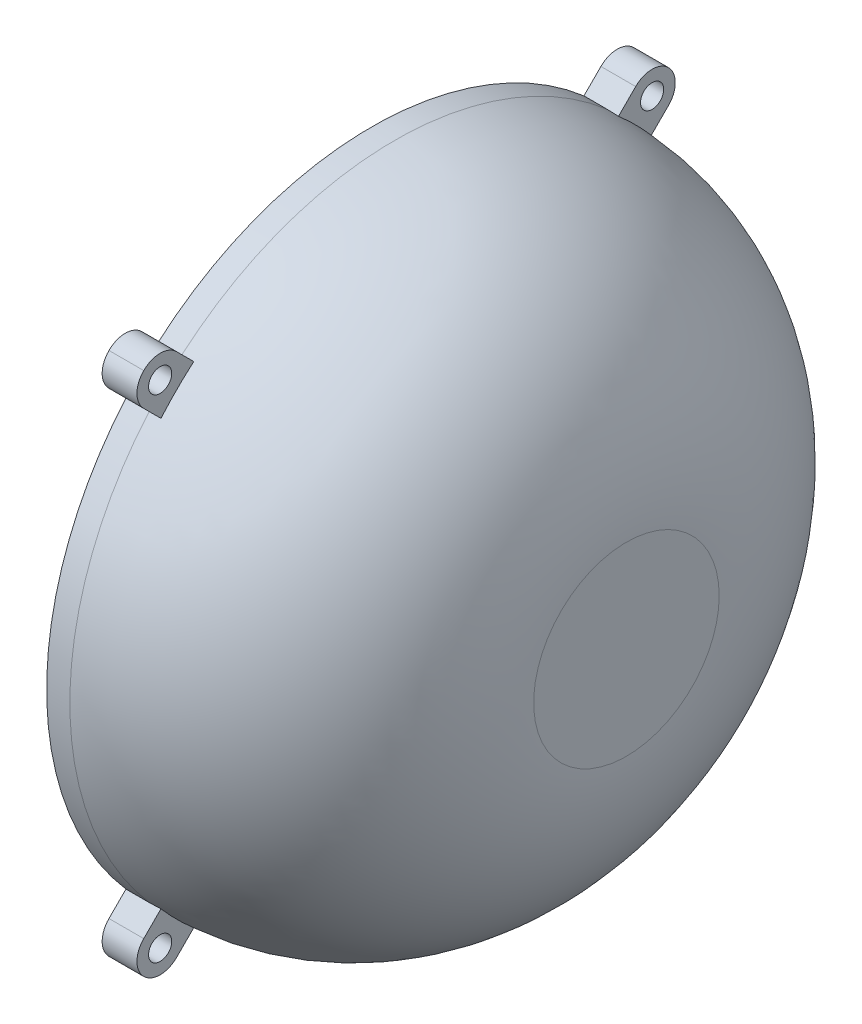
SolidWorks part; units mm, degrees
ref_plane "Front Plane" through (0, 0, 0) normal (0, 0, 1) x (1, 0, 0)
ref_plane "Top Plane" through (0, 0, 0) normal (0, 1, 0) x (1, 0, 0)
ref_plane "Right Plane" through (0, 0, 0) normal (1, 0, 0) x (0, 0, -1)
sketch "Sketch1" plane through (0, 0, 0) normal (1, 0, 0) x (0, 0, -1)
  circle A0 centre (0, 0) radius 70
  dimension "D1" = 140
extrude "Boss-Extrude1" add sketch "Sketch1" along normal blind 55
fillet "Fillet1" radius 50 1 edges at (55, 0, -70)
shell "Shell1" thickness 2.5
sketch "Sketch2" plane through (0, 0, 0) normal (-1, 0, 0) x (0, 0, 1)
  circle A0 centre (0, 0) radius 67.5
  dimension "D1" = 135
extrude "Cut-Extrude1" cut sketch "Sketch2" against normal blind 6
sketch "Sketch3" plane through (0, 0, 0) normal (-1, 0, 0) x (0, 0, 1)
  line L0 (0, 0) -> (-64.1896, 64.1896) construction
  line L1 (-48.7923, 48.7923) -> (-45.2568, 52.3278)
  line L2 (-45.2568, 52.3278) -> (-53.033, 60.1041)
  line L3 (-53.033, 60.1041) -> (-60.1041, 53.033)
  line L4 (-60.1041, 53.033) -> (-52.3278, 45.2568)
  line L5 (-52.3278, 45.2568) -> (-48.7923, 48.7923)
  line L6 (45.2568, 52.3278) -> (48.7923, 48.7923)
  line L7 (48.7923, 48.7923) -> (52.3278, 45.2568)
  line L8 (52.3278, 45.2568) -> (60.1041, 53.033)
  line L9 (60.1041, 53.033) -> (53.033, 60.1041)
  line L10 (53.033, 60.1041) -> (45.2568, 52.3278)
  line L11 (52.3278, -45.2568) -> (48.7923, -48.7923)
  line L12 (48.7923, -48.7923) -> (45.2568, -52.3278)
  line L13 (45.2568, -52.3278) -> (53.033, -60.1041)
  line L14 (53.033, -60.1041) -> (60.1041, -53.033)
  line L15 (60.1041, -53.033) -> (52.3278, -45.2568)
  line L16 (-45.2568, -52.3278) -> (-48.7923, -48.7923)
  line L17 (-48.7923, -48.7923) -> (-52.3278, -45.2568)
  line L18 (-52.3278, -45.2568) -> (-60.1041, -53.033)
  line L19 (-60.1041, -53.033) -> (-53.033, -60.1041)
  line L20 (-53.033, -60.1041) -> (-45.2568, -52.3278)
  point P26 (0, 0)
  dimension "D1" = 5
  dimension "D2" = 5
  dimension "D3" = 80
  dimension "D4" = 4
extrude "Boss-Extrude2" add sketch "Sketch3" against normal blind 7.5
fillet "Fillet2" radius 5 8 edges at (3.75, 60.1041, -53.033) (3.75, 53.033, -60.1041) (3.75, -53.033, -60.1041) (3.75, -60.1041, -53.033) (3.75, -60.1041, 53.033) (3.75, -53.033, 60.1041) (3.75, 53.033, 60.1041) (3.75, 60.1041, 53.033)
sketch "Sketch4" plane through (0, 0, 0) normal (-1, 0, 0) x (0, 0, 1)
  circle A0 centre (-53.033, 53.033) radius 2.5
  circle A1 centre (53.033, 53.033) radius 2.5
  circle A2 centre (53.033, -53.033) radius 2.5
  circle A3 centre (-53.033, -53.033) radius 2.5
  dimension "D1" = 5
  dimension "D2" = 5
  dimension "D3" = 5
  dimension "D4" = 5
extrude "Cut-Extrude2" cut sketch "Sketch4" against normal blind 7.5
